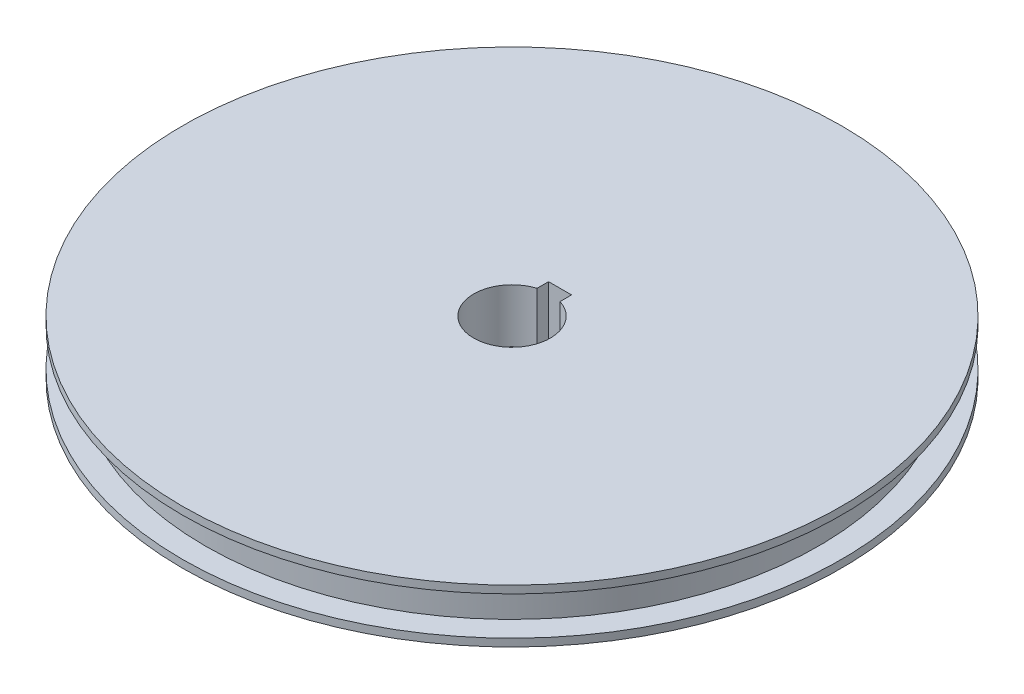
SolidWorks part; units mm, degrees
material "ABS PC"
ref_plane "Front Plane" through (0, 0, 0) normal (0, 0, 1) x (1, 0, 0)
ref_plane "Top Plane" through (0, 0, 0) normal (0, 1, 0) x (1, 0, 0)
ref_plane "Right Plane" through (0, 0, 0) normal (1, 0, 0) x (0, 0, -1)
sketch "Sketch1" plane through (0, 0, 0) normal (0, 1, 0) x (1, 0, 0)
  line L0 (0, 0) -> (0, 22.1757) construction
  line L3 (-1.5, 4.7697) -> (-1.5, 6.2697)
  line L4 (-1.5, 6.2697) -> (1.5, 6.2697)
  line L5 (1.5, 4.7697) -> (1.5, 6.2697)
  circle A0 centre (0, 0) radius 5
  circle A1 centre (0, 0) radius 40
  circle A2 centre (0, 0) radius 43
  dimension "D1" = 80
  dimension "D2" = 10
  dimension "D3" = 3
  dimension "D4" = 1.5
  dimension "D5" = 3
extrude "Boss-Extrude1" add sketch "Sketch1" along normal blind 5 contours A1 A0 region at (-38.8686, 0, 0)
extrude "Boss-Extrude2" add sketch "Sketch1<3>" against normal blind 1 contours A1 A0 | A2 A1 region at (-38.8686, 0, 0) region at (-41.7838, 0, 0)
sketch "Sketch1<3>" plane through (0, 0, 0) normal (0, 1, 0) x (1, 0, 0) same geometry as "Sketch1"
extrude "Boss-Extrude3" add sketch "Sketch1<4>" along normal blind 1 from surface contours A1 A0 | A2 A1 region at (-38.8686, 0, 0) region at (-41.7838, 0, 0) starting at face at (0, 5, -3.0773)
sketch "Sketch1<4>" plane through (0, 0, 0) normal (0, 1, 0) x (1, 0, 0) same geometry as "Sketch1"
